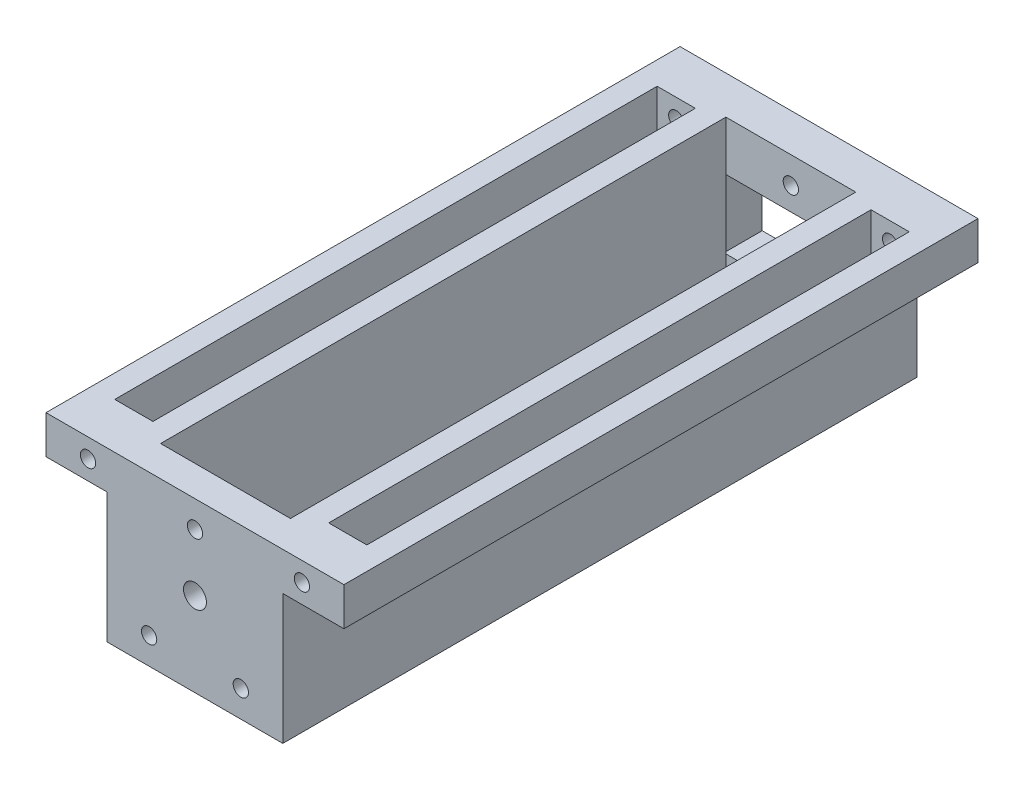
SolidWorks part; units mm, degrees
ref_plane "Front Plane" through (0, 0, 0) normal (0, 0, 1) x (1, 0, 0)
ref_plane "Top Plane" through (0, 0, 0) normal (0, 1, 0) x (1, 0, 0)
ref_plane "Right Plane" through (0, 0, 0) normal (1, 0, 0) x (0, 0, -1)
sketch "Sketch1" plane through (0, 0, 0) normal (0, 0, 1) x (1, 0, 0)
  line L0 (-76.2, -95.25) -> (76.2, -95.25) construction
  line L1 (-146.05, 139.7) -> (146.05, 139.7)
  line L2 (-146.05, 139.7) -> (-146.05, -139.7)
  line L3 (-146.05, -139.7) -> (146.05, -139.7)
  line L4 (146.05, 139.7) -> (146.05, -139.7)
  line L5 (-146.05, 139.7) -> (146.05, -139.7) construction
  line L6 (-146.05, -139.7) -> (146.05, 139.7) construction
  line L11 (-111.125, -57.15) -> (111.125, -57.15)
  line L12 (-111.125, -57.15) -> (-111.125, 57.15)
  line L13 (-111.125, 57.15) -> (111.125, 57.15)
  line L14 (111.125, -57.15) -> (111.125, 57.15)
  line L15 (-111.125, -57.15) -> (111.125, 57.15) construction
  line L16 (-111.125, 57.15) -> (111.125, -57.15) construction
  line L18 (-44.45, -139.7) -> (44.45, -139.7)
  line L19 (-44.45, -139.7) -> (-44.45, -57.15)
  line L20 (-44.45, -57.15) -> (44.45, -57.15)
  line L21 (44.45, -139.7) -> (44.45, -57.15)
  line L22 (-44.45, -139.7) -> (44.45, -57.15) construction
  line L23 (-44.45, -57.15) -> (44.45, -139.7) construction
  circle A0 centre (0, 95.25) radius 12.7
  circle A1 centre (0, -95.25) radius 12.7
  circle A2 centre (76.2, -95.25) radius 12.7
  circle A3 centre (-76.2, -95.25) radius 12.7
  point P0 (0, 0)
  point P11 (0, 0)
  point P12 (0, 0)
  point P19 (0, -95.25)
  point P20 (0, -98.425)
  point P26 (32.5345, -139.7)
  point P27 (0, 0)
  dimension "D1" = 25.4
  dimension "D9" = 152.4
  dimension "D2" = 292.1
  dimension "D3" = 44.45
  dimension "D4" = 44.45
  dimension "D5" = 222.25
  dimension "D6" = 114.3
  dimension "D7" = 95.25
  dimension "D8" = 95.25
  dimension "D10" = 88.9
extrude "Boss-Extrude1" add sketch "Sketch1" along normal blind 63.5 contours L21 L3 L4 L1 L2 L19 L11 L12 L13 L14 A3 A2 A0 region at (0, 135.6579, 0)
sketch "Sketch2" plane through (0, 139.7, 0) normal (0, 1, 0) x (1, 0, 0)
  line L1 (-107.95, -1003.3) -> (-146.05, -1003.3)
  line L2 (-107.95, -1003.3) -> (-107.95, -63.5)
  line L3 (-107.95, -63.5) -> (-146.05, -63.5)
  line L4 (-146.05, -1003.3) -> (-146.05, -63.5)
  line L5 (-107.95, -1003.3) -> (-146.05, -63.5) construction
  line L6 (-107.95, -63.5) -> (-146.05, -1003.3) construction
  line L7 (107.95, -1003.3) -> (146.05, -1003.3)
  line L8 (107.95, -1003.3) -> (107.95, -63.5)
  line L9 (107.95, -63.5) -> (146.05, -63.5)
  line L10 (146.05, -1003.3) -> (146.05, -63.5)
  line L11 (107.95, -1003.3) -> (146.05, -63.5) construction
  line L12 (107.95, -63.5) -> (146.05, -1003.3) construction
  point P0 (-127, -533.4)
  point P5 (127, -533.4)
  point P11 (-107.95, -479.573)
  point P12 (146.05, -556.7669)
  point P14 (146.05, -63.5)
  point P16 (-146.05, -63.5)
  dimension "D1" = 38.1
  dimension "D2" = 939.8
extrude "Boss-Extrude2" add sketch "Sketch2" against normal up to surface (279.4 mm away) up to face at (-95.25, -139.7, 31.75)
sketch "Sketch3" plane through (0, 0, 1003.3) normal (0, 0, 1) x (1, 0, 0)
  line L4 (-146.05, 139.7) -> (146.05, 139.7)
  line L5 (-146.05, -139.7) -> (146.05, -139.7)
  line L8 (107.95, -139.7) -> (146.05, -139.7)
  line L9 (146.05, -139.7) -> (146.05, 139.7)
  line L10 (146.05, 139.7) -> (107.95, 139.7)
  line L11 (107.95, 139.7) -> (107.95, -139.7)
  line L12 (107.95, -139.7) -> (146.05, -139.7)
  line L13 (146.05, -139.7) -> (146.05, 139.7)
  line L14 (146.05, 139.7) -> (107.95, 139.7)
  line L16 (-146.05, -139.7) -> (-107.95, -139.7)
  line L17 (-107.95, -139.7) -> (-107.95, 139.7)
  line L18 (-107.95, 139.7) -> (-146.05, 139.7)
  line L19 (-146.05, 139.7) -> (-146.05, -139.7)
  line L20 (-146.05, -139.7) -> (-107.95, -139.7)
  line L22 (-107.95, 139.7) -> (-146.05, 139.7)
  line L23 (-146.05, 139.7) -> (-146.05, -139.7)
  circle A0 centre (76.2, -95.25) radius 12.7 construction
  circle A1 centre (-76.2, -95.25) radius 12.7 construction
  circle A2 centre (0, 95.25) radius 12.7 construction
  circle A3 centre (76.2, -95.25) radius 12.7
  circle A4 centre (-76.2, -95.25) radius 12.7
  circle A5 centre (0, 95.25) radius 12.7
  line M9 (-146.05, -139.7) -> (-107.95, -139.7)
  line M10 (-107.95, -139.7) -> (-107.95, 139.7)
  line M11 (-107.95, 139.7) -> (-146.05, 139.7)
  line M12 (-146.05, 139.7) -> (-146.05, -139.7)
  dimension "D1" = 0
  dimension "D2" = 0
extrude "Boss-Extrude3" add sketch "Sketch3" along normal blind 50.8 contours L5 L13 L4 A5 A4 A3 M10 | M12 M9 M10 M11 region at (-127, 0, 1003.3) region at (0, 0.8208, 1003.3) region at (127, 0, 1003.3)
sketch "Sketch4" plane through (0, 0, 1054.1) normal (0, 0, 1) x (1, 0, 0)
  circle A0 centre (0, 0) radius 19.05
  dimension "D1" = 38.1
extrude "Cut-Extrude1" cut sketch "Sketch4" against normal up to next
sketch "Sketch5" plane through (0, 0, 1054.1) normal (0, 0, 1) x (1, 0, 0)
  line L0 (-146.05, 139.7) -> (146.05, 139.7) construction
  line L1 (247.65, 76.2) -> (146.05, 76.2)
  line L2 (247.65, 76.2) -> (247.65, 139.7)
  line L3 (247.65, 139.7) -> (146.05, 139.7)
  line L4 (146.05, 76.2) -> (146.05, 139.7)
  line L5 (247.65, 76.2) -> (146.05, 139.7) construction
  line L6 (247.65, 139.7) -> (146.05, 76.2) construction
  line L7 (209.55, 76.2) -> (247.65, 76.2)
  line L8 (209.55, 76.2) -> (209.55, 139.7)
  line L9 (209.55, 139.7) -> (247.65, 139.7)
  line L10 (247.65, 76.2) -> (247.65, 139.7)
  line L11 (209.55, 76.2) -> (247.65, 139.7) construction
  line L12 (209.55, 139.7) -> (247.65, 76.2) construction
  line L13 (-247.65, 76.2) -> (-146.05, 76.2)
  line L14 (-247.65, 76.2) -> (-247.65, 139.7)
  line L15 (-247.65, 139.7) -> (-146.05, 139.7)
  line L16 (-146.05, 76.2) -> (-146.05, 139.7)
  line L17 (-247.65, 76.2) -> (-146.05, 139.7) construction
  line L18 (-247.65, 139.7) -> (-146.05, 76.2) construction
  line L19 (-146.05, 139.7) -> (-146.05, -139.7) construction
  line L20 (146.05, 107.95) -> (209.55, 107.95) construction
  line L21 (-209.55, 76.2) -> (-247.65, 76.2)
  line L22 (-209.55, 76.2) -> (-209.55, 139.7)
  line L23 (-209.55, 139.7) -> (-247.65, 139.7)
  line L24 (-247.65, 76.2) -> (-247.65, 139.7)
  line L25 (-209.55, 76.2) -> (-247.65, 139.7) construction
  line L26 (-209.55, 139.7) -> (-247.65, 76.2) construction
  line L27 (-209.55, 107.95) -> (-146.05, 107.95) construction
  circle A0 centre (177.8, 107.95) radius 12.7
  circle A1 centre (-177.8, 107.95) radius 12.7
  point P0 (196.85, 107.95)
  point P6 (228.6, 107.95)
  point P8 (-196.85, 107.95)
  point P19 (146.05, 107.95)
  point P20 (-228.6, 107.95)
  point P30 (177.8, 107.95)
  point P33 (201.5842, 76.2)
  line M14 (146.05, -139.7) -> (146.05, 139.7)
  line M16 (-146.05, 139.7) -> (-146.05, -139.7)
  dimension "D5" = 25.4
  dimension "D1" = 38.1
  dimension "D2" = 38.1
  dimension "D3" = 63.5
  dimension "D4" = 355.6
extrude "Boss-Extrude4" add sketch "Sketch5" against normal blind 76.2 contours L13 L22 L15 L14 | L22 L13 L15 M16 | L1 L8 L3 M14 | L8 L1 L2 L3 region at (228.6, 107.95, 1054.1) region at (177.8, 77.098, 1054.1) region at (-228.6, 107.95, 1054.1) region at (-208.652, 107.95, 1054.1)
extrude "Boss-Extrude5" add sketch "Sketch5<3>" along normal blind 76.2 from surface contours L1 L8 L3 M14 | L8 L1 L2 L3 | L13 L22 L15 L14 | L22 L13 L15 M16 region at (228.6, 107.95, 1054.1) region at (177.8, 77.098, 1054.1) region at (-228.6, 107.95, 1054.1) region at (-208.652, 107.95, 1054.1) starting at face at (-63.5, -95.25, 0)
sketch "Sketch5<3>" plane through (0, 0, 1054.1) normal (0, 0, 1) x (1, 0, 0) same geometry as "Sketch5"
extrude "Boss-Extrude6" add sketch "Sketch5<4>" against normal up to surface (977.9 mm away) from surface contours L13 L22 L15 L14 | L8 L1 L2 L3 region at (228.6, 107.95, 1054.1) region at (-228.6, 107.95, 1054.1) up to face at (196.85, 107.95, 76.2) starting at face at (190.5, 107.95, 977.9)
sketch "Sketch5<4>" plane through (0, 0, 1054.1) normal (0, 0, 1) x (1, 0, 0) same geometry as "Sketch5"
